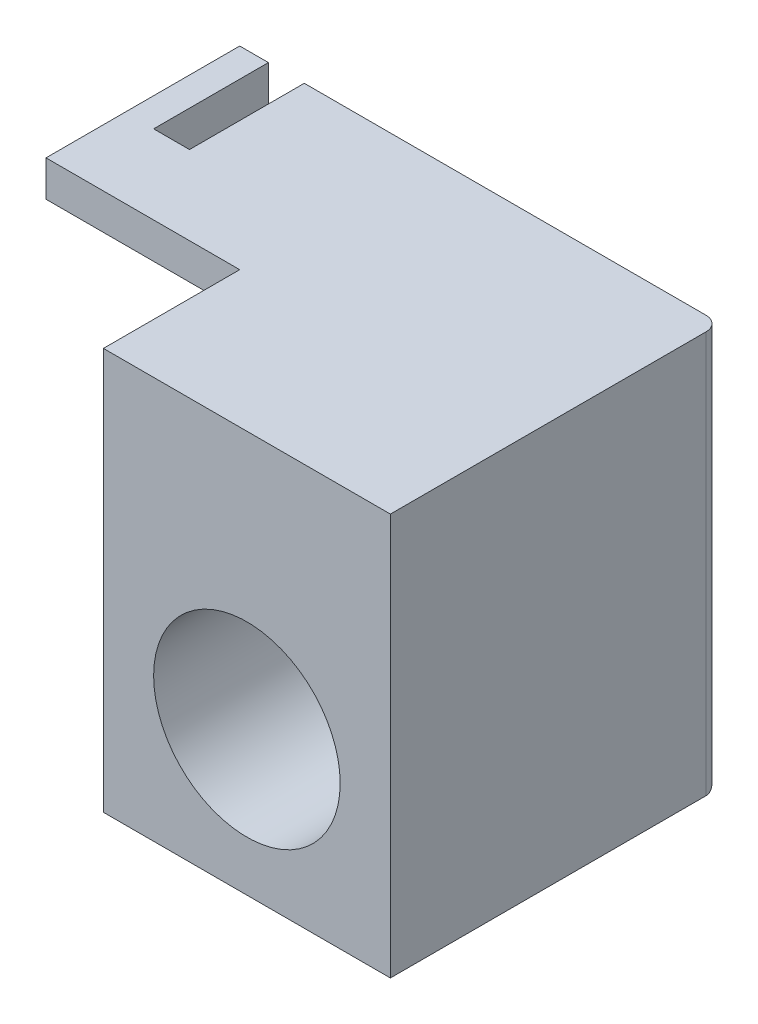
SolidWorks part; units mm, degrees
ref_plane "Front Plane" through (0, 0, 0) normal (0, 0, 1) x (1, 0, 0)
ref_plane "Top Plane" through (0, 0, 0) normal (0, 1, 0) x (1, 0, 0)
ref_plane "Right Plane" through (0, 0, 0) normal (1, 0, 0) x (0, 0, -1)
sketch "Sketch1" plane through (0, 0, 0) normal (0, 0, 1) x (1, 0, 0)
  line L1 (0, 0) -> (-20, 0)
  line L2 (0, 0) -> (0, -28)
  line L3 (0, -28) -> (-20, -28)
  line L4 (-20, 0) -> (-20, -28)
  dimension "D1" = 20
  dimension "D2" = 28
extrude "Boss-Extrude1" add sketch "Sketch1" along normal blind 23
sketch "Sketch2" plane through (0, 0, 23) normal (0, 0, 1) x (1, 0, 0)
  line L0 (-20, 0) -> (-20, -28) construction
  line L1 (0, 0) -> (-20, 0) construction
  circle A0 centre (-10, -18) radius 6.5
  point P4 (-20, -14)
  point P7 (-10, 0)
  dimension "D1" = 4
  dimension "D2" = 0
  dimension "D3" = 13
extrude "Cut-Extrude1" cut sketch "Sketch2" against normal blind 40
sketch "Sketch3" plane through (-20, 0, 0) normal (-1, 0, 0) x (0, 0, 1)
  line L1 (0, 0) -> (0, -28) construction
  circle A0 centre (8, -18) radius 2.75
  point P7 (0, -14)
  dimension "D1" = 8
  dimension "D2" = 4
  dimension "D3" = 5.5
extrude "Cut-Extrude2" cut sketch "Sketch3" against normal blind 10
thread "Thread1" pitch 2.1167 method cut profile "Thread Profile1" start angle 0, offset 0, length 10, pitch 2.1167, diameter 5.5
ref_plane "Plane1" through (-20, -18, 5.25) normal (0, -1, 0) x (0, 0, -1)
sketch "Thread Profile1" plane through (-20, -18, 5.25) normal (0, -1, 0) x (0, 0, -1)
  line L0 (0, 0) -> (0, 2.1167) construction
  line L1 (0, 0) -> (1.1457, 0.6615)
  line L2 (1.1457, 0.6615) -> (1.1457, 0.926)
  line L3 (1.1457, 0.926) -> (0, 1.5875)
  line L4 (1.1457, 0.7937) -> (0, 0.7937) construction
  line L11 (0, 0) -> (0, 1.5875)
  point P2 (0, 0)
  dimension "Pitch" = 2.1167
  dimension "Profile_Angle" = 60
  dimension "Profile_Land" = 0.2646
  dimension "Profile_Height" = 1.1457
sketch "Sketch6" plane through (-20, 0, 0) normal (-1, 0, 0) x (0, 0, 1)
  circle A0 centre (8, -18) radius 3.75
  dimension "D1" = 7.5
extrude "Cut-Extrude3" cut sketch "Sketch6" against normal blind 1
sketch "Sketch7" plane through (-20, 0, 0) normal (-1, 0, 0) x (0, 0, 1)
  line L0 (23, 0) -> (0, 0) construction
  line L1 (0, -2.5) -> (13.5, -2.5)
  line L2 (0, -2.5) -> (0, 0)
  line L3 (0, 0) -> (13.5, 0)
  line L4 (13.5, -2.5) -> (13.5, 0)
  line L5 (0, 0) -> (0, -28) construction
  dimension "D1" = 0
  dimension "D2" = 0
  dimension "D3" = 2.5
  dimension "D4" = 13.5
extrude "Boss-Extrude2" add sketch "Sketch7" along normal blind 13.5
sketch "Sketch8" plane through (0, -2.5, 0) normal (0, -1, 0) x (-1, 0, 0)
  line L0 (33.5, 0) -> (20, 0) construction
  line L1 (31.5, 0) -> (29, 0)
  line L2 (31.5, 0) -> (31.5, -8)
  line L3 (31.5, -8) -> (29, -8)
  line L4 (29, 0) -> (29, -8)
  line L5 (33.5, 0) -> (33.5, -13.5) construction
  dimension "D1" = 8
  dimension "D2" = 2
  dimension "D3" = 2.5
extrude "Cut-Extrude4" cut sketch "Sketch8" against normal blind 10
fillet "Fillet1" radius 1 3 edges at (-10, -28, 0) (-20, -15.25, 0) (0, -14, 0)
